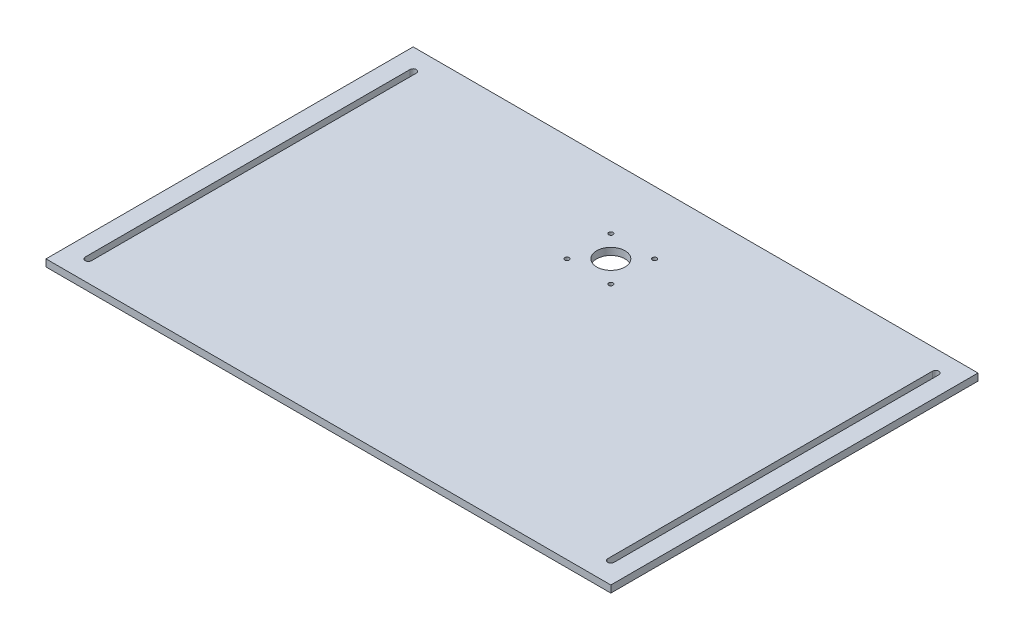
SolidWorks part; units mm, degrees
ref_plane "前基準面" through (0, 0, 0) normal (0, 0, 1) x (1, 0, 0)
ref_plane "上基準面" through (0, 0, 0) normal (0, 1, 0) x (1, 0, 0)
ref_plane "右基準面" through (0, 0, 0) normal (1, 0, 0) x (0, 0, -1)
sketch "草圖1" plane through (0, 0, 0) normal (0, 1, 0) x (1, 0, 0)
  line L0 (200, 60) -> (170, 60) construction
  line L1 (200, 160) -> (-200, 160) construction
  line L2 (200, 160) -> (200, -160) construction
  line L3 (200, -160) -> (-200, -160) construction
  line L4 (-200, 160) -> (-200, -160) construction
  line L5 (0, -160) -> (0, 160) construction
  line L6 (200, 0) -> (-200, 0) construction
  line L7 (-200, 160) -> (200, 160) construction
  line L8 (-200, 160) -> (-200, 130) construction
  line L9 (-200, 130) -> (200, 130) construction
  line L10 (200, 160) -> (200, 130) construction
  line L11 (-200, 130) -> (-170, 130) construction
  line L12 (-200, 130) -> (-200, -130) construction
  line L13 (-200, -130) -> (-170, -130) construction
  line L14 (-170, 130) -> (-170, -130) construction
  line L15 (200, -160) -> (-200, -160) construction
  line L16 (200, -160) -> (200, -130) construction
  line L17 (200, -130) -> (-200, -130) construction
  line L18 (-200, -160) -> (-200, -130) construction
  line L19 (200, -130) -> (170, -130) construction
  line L20 (200, -130) -> (200, 130) construction
  line L21 (200, 130) -> (170, 130) construction
  line L22 (170, -130) -> (170, 130) construction
  line L23 (-200, 130) -> (-170, 130) construction
  line L24 (-200, 130) -> (-200, 60) construction
  line L25 (-200, 60) -> (-170, 60) construction
  line L26 (-170, 130) -> (-170, 60) construction
  line L27 (170, 130) -> (170, 60) construction
  line L29 (200, 130) -> (200, 60) construction
  line L30 (-200, -60) -> (-170, -60) construction
  line L31 (-170, -130) -> (-170, -60) construction
  line L32 (-200, -130) -> (-170, -130) construction
  line L33 (-200, -130) -> (-200, -60) construction
  line L34 (200, -130) -> (200, -60) construction
  line L35 (170, -130) -> (170, -60) construction
  line L36 (200, -60) -> (170, -60) construction
  line L37 (200, -130) -> (170, -130) construction
  line L40 (-200, 130) -> (-200, -130)
  line L42 (200, 130) -> (200, -130)
  line L43 (-200, 130) -> (200, 130)
  line L44 (-200, 130) -> (-200, -130)
  line L45 (-200, -130) -> (200, -130)
  line L46 (200, 130) -> (200, -130)
  point P0 (0, 0)
  dimension "D1" = 400
  dimension "D2" = 320
  dimension "D4" = 30
  dimension "D6" = 30
  dimension "D7" = 70
extrude "填料-伸長1" add sketch "草圖1" along normal blind 5 contours L40 L45 L42 L43 region at (0, 0, 0)
sketch "草圖2" plane through (0, 5, 0) normal (0, 1, 0) x (1, 0, 0)
  line L0 (-185, 130) -> (-185, -130) construction
  line L1 (-200, 130) -> (200, 130) construction
  line L2 (-200, -130) -> (200, -130) construction
  line L3 (185, -130) -> (185, 130) construction
  line L4 (-185, 115) -> (-185, -115) construction
  line L5 (-182.75, 115) -> (-182.75, -115)
  line L6 (-187.25, 115) -> (-187.25, -115)
  line L7 (-200, 60) -> (-170, 60) construction
  line L8 (200, 0) -> (-200, 0) construction
  line L9 (0, -160) -> (0, 160) construction
  line L10 (0, -160) -> (0, 160) construction
  line L11 (185, 115) -> (185, -115) construction
  line L12 (182.75, 115) -> (182.75, -115)
  line L13 (187.25, 115) -> (187.25, -115)
  arc A0 (-182.75, 115) -> (-187.25, 115) centre (-185, 115) ccw
  arc A1 (-187.25, -115) -> (-182.75, -115) centre (-185, -115) ccw
  arc A2 (182.75, 115) -> (187.25, 115) centre (185, 115) cw
  arc A3 (187.25, -115) -> (182.75, -115) centre (185, -115) cw
  point P10 (-185, 0)
  point P17 (-185, 60)
  point P25 (185, 0)
  dimension "D1" = 4.5
  dimension "D2" = 230
extrude "除料-伸長1" cut sketch "草圖2" against normal through all
sketch "草圖3" plane through (0, 5, 0) normal (0, 1, 0) x (1, 0, 0)
  line L0 (0, -160) -> (0, 160) construction
  line L5 (-200, 130) -> (-200, -130) construction
  line L10 (-200, 190) -> (200, 190) construction
  line L11 (-200, 190) -> (-200, 130) construction
  line L12 (-200, 130) -> (200, 130) construction
  line L13 (-21.15, 85.5) -> (-15.5, 91.15) construction
  line L14 (-15.5, 91.15) -> (15.5, 91.15) construction
  line L15 (-21.15, 85.5) -> (-21.15, 54.5) construction
  line L16 (-15.5, 48.85) -> (15.5, 48.85) construction
  line L17 (21.15, 85.5) -> (21.15, 54.5) construction
  line L18 (15.5, 91.15) -> (21.15, 85.5) construction
  line L19 (15.5, 48.85) -> (21.15, 54.5) construction
  line L20 (-21.15, 54.5) -> (-15.5, 48.85) construction
  line L21 (200, 190) -> (200, 130) construction
  circle A4 centre (-15.5, 85.5) radius 1.55
  circle A5 centre (15.5, 85.5) radius 1.55
  circle A6 centre (-15.5, 54.5) radius 1.55
  circle A7 centre (15.5, 54.5) radius 1.55
  circle A8 centre (0, 70) radius 10
  point P0 (0, 70)
  point P32 (0, 91.15)
  point P50 (-21.15, 70)
  dimension "D2" = 42.3
  dimension "D10" = 45
  dimension "D5" = 3.1
  dimension "D11" = 20
  dimension "D1" = 42.3
  dimension "D3" = 31
  dimension "D4" = 31
  dimension "D7" = 5.65
  dimension "D8" = 60
  dimension "D9" = 60
  dimension "D6" = 5.65
extrude "除料-伸長2" cut sketch "草圖3" against normal through all
